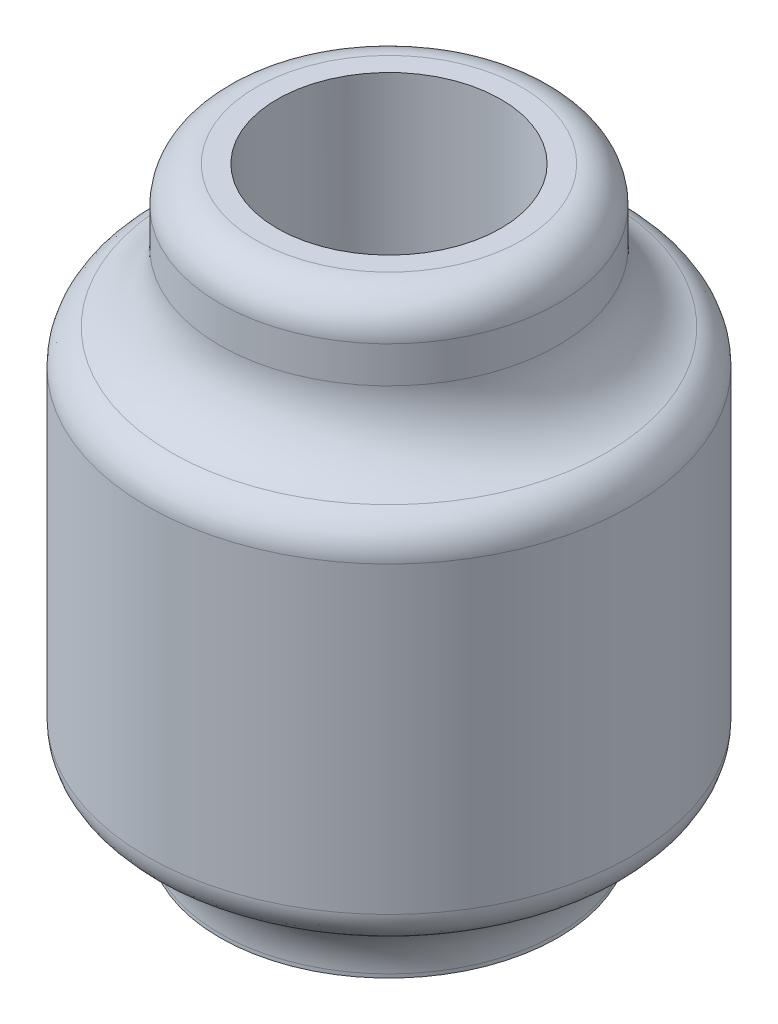
SolidWorks part; units mm, degrees
ref_plane "Front Plane" through (0, 0, 0) normal (0, 0, 1) x (1, 0, 0)
ref_plane "Top Plane" through (0, 0, 0) normal (0, 1, 0) x (1, 0, 0)
ref_plane "Right Plane" through (0, 0, 0) normal (1, 0, 0) x (0, 0, -1)
sketch "Sketch1" plane through (0, 0, 0) normal (0, 1, 0) x (1, 0, 0)
  circle A0 centre (0, 0) radius 6.15
  circle A1 centre (0, 0) radius 9.3
  dimension "D1" = 12.3
  dimension "D2" = 18.6
extrude "Boss-Extrude1" add sketch "Sketch1" along normal blind 12.2
sketch "Sketch2" plane through (0, 12.2, 0) normal (0, 1, 0) x (1, 0, 0)
  circle A0 centre (0, 0) radius 6.15 construction
  circle A1 centre (0, 0) radius 9.3
  circle A2 centre (0, 0) radius 9.3
  circle A3 centre (0, 0) radius 6.15
  dimension "D1" = 0
extrude "Boss-Extrude2" add sketch "Sketch2" along normal blind 12 from offset 4 separate body
sketch "Sketch3" plane through (0, 12.2, 0) normal (0, 1, 0) x (1, 0, 0)
  circle A2 centre (0, 0) radius 13.3
  circle A3 centre (0, 0) radius 13.3
  circle A4 centre (0, 0) radius 12.3
  dimension "D2" = 1
  dimension "D1" = 4
extrude "Boss-Extrude3" add sketch "Sketch3" along normal blind 10 and the other way blind 6 separate body
sketch "Sketch4" plane through (0, 22.2, 0) normal (0, 1, 0) x (1, 0, 0)
  circle A0 centre (0, 0) radius 9.3
  circle A1 centre (0, 0) radius 13.3
  circle A2 centre (0, 0) radius 13.3
  circle A3 centre (0, 0) radius 9.3 construction
  dimension "D2" = 0
  dimension "D1" = 0
extrude "Boss-Extrude4" add sketch "Sketch4" along normal blind 2
sketch "Sketch5" plane through (0, 0, 0) normal (0, -1, 0) x (1, 0, 0)
  line L1 (0.8029, 2.2849) -> (11.4839, 2.2849)
  line L2 (0.8029, 2.2849) -> (0.8029, -1.7151)
  line L3 (0.8029, -1.7151) -> (11.4839, -1.7151)
  line L4 (11.4839, 2.2849) -> (11.4839, -1.7151)
  line L5 (0.8029, 2.2849) -> (11.4839, -1.7151) construction
  line L6 (0.8029, -1.7151) -> (11.4839, 2.2849) construction
  line L7 (-2, 0.3278) -> (2, 0.3278)
  line L8 (-2, 0.3278) -> (-2, -12.6278)
  line L9 (-2, -12.6278) -> (2, -12.6278)
  line L10 (2, 0.3278) -> (2, -12.6278)
  line L11 (-2, 0.3278) -> (2, -12.6278) construction
  line L12 (-2, -12.6278) -> (2, 0.3278) construction
  line L13 (-2.4261, 2) -> (-9.8739, 2)
  line L14 (-2.4261, 2) -> (-2.4261, -2)
  line L15 (-2.4261, -2) -> (-9.8739, -2)
  line L16 (-9.8739, 2) -> (-9.8739, -2)
  line L17 (-2.4261, 2) -> (-9.8739, -2) construction
  line L18 (-2.4261, -2) -> (-9.8739, 2) construction
  line L19 (-2, 1.9767) -> (2, 1.9767)
  line L20 (-2, 1.9767) -> (-2, 10.3233)
  line L21 (-2, 10.3233) -> (2, 10.3233)
  line L22 (2, 1.9767) -> (2, 10.3233)
  line L23 (-2, 1.9767) -> (2, 10.3233) construction
  line L24 (-2, 10.3233) -> (2, 1.9767) construction
  circle A0 centre (0, 0) radius 6.15 construction
  point P0 (6.1434, 0.2849)
  point P7 (0, -6.15)
  point P12 (-6.15, 0)
  point P17 (0, 6.15)
  circle M5 centre (0, 0) radius 9.3
  circle M6 centre (0, 0) radius 6.15
  dimension "D1" = 4
  dimension "D2" = 4
  dimension "D3" = 4
  dimension "D4" = 4
extrude "Cut-Extrude1" cut sketch "Sketch5" against normal blind 6 from offset 6 contours L3 L1 M6 M5 | L10 L8 M6 M5 | L15 L13 M6 M5 | L22 L20 M6 M5 region at (7.6269, 0, 0.2919) region at (0, 0, 7.6329) region at (-7.6329, 0, 0) region at (0, 0, -7.6329) offset against normal yes
sketch "Sketch6" plane through (0, 0, 0) normal (0, -1, 0) x (1, 0, 0)
  line L1 (-2, -0.1222) -> (2, -0.1222)
  line L2 (-2, -0.1222) -> (-2, -12.1778)
  line L3 (-2, -12.1778) -> (2, -12.1778)
  line L4 (2, -0.1222) -> (2, -12.1778)
  line L5 (-2, -0.1222) -> (2, -12.1778) construction
  line L6 (-2, -12.1778) -> (2, -0.1222) construction
  line L7 (1.8378, 2) -> (10.4622, 2)
  line L8 (1.8378, 2) -> (1.8378, -2)
  line L9 (1.8378, -2) -> (10.4622, -2)
  line L10 (10.4622, 2) -> (10.4622, -2)
  line L11 (1.8378, 2) -> (10.4622, -2) construction
  line L12 (1.8378, -2) -> (10.4622, 2) construction
  line L13 (-1.6491, 2) -> (-10.6509, 2)
  line L14 (-1.6491, 2) -> (-1.6491, -2)
  line L15 (-1.6491, -2) -> (-10.6509, -2)
  line L16 (-10.6509, 2) -> (-10.6509, -2)
  line L17 (-1.6491, 2) -> (-10.6509, -2) construction
  line L18 (-1.6491, -2) -> (-10.6509, 2) construction
  line L19 (2, 14.7464) -> (-2, 14.7464)
  line L20 (2, 14.7464) -> (2, 3.8536)
  line L21 (2, 3.8536) -> (-2, 3.8536)
  line L22 (-2, 14.7464) -> (-2, 3.8536)
  line L23 (2, 14.7464) -> (-2, 3.8536) construction
  line L24 (2, 3.8536) -> (-2, 14.7464) construction
  circle A0 centre (0, 0) radius 6.15 construction
  circle A1 centre (0, 0) radius 9.3 construction
  point P0 (0, -6.15)
  point P7 (6.15, 0)
  point P12 (-6.15, 0)
  point P17 (0, 9.3)
  circle M5 centre (0, 0) radius 9.3
  circle M6 centre (0, 0) radius 6.15
  dimension "D1" = 4
  dimension "D2" = 4
  dimension "D3" = 4
  dimension "D4" = 4
extrude "Cut-Extrude2" cut sketch "Sketch6" against normal blind 6 from offset 16 contours L4 L2 M6 M5 | L15 L13 M6 M5 | L22 L20 M5 M6 | L9 L7 M6 M5 region at (0, 0, -7.6329) region at (-7.6329, 0, 0) region at (7.6329, 0, 0) region at (0, 0, 7.6329) offset against normal yes
sketch "Sketch7" plane through (0, 16.2, 0) normal (0, -1, 0) x (1, 0, 0)
  circle A0 centre (0, 0) radius 9.3
extrude "Boss-Extrude5" add sketch "Sketch7" along normal blind 4
sketch "Sketch8" plane through (0, 6.2, 0) normal (0, -1, 0) x (1, 0, 0)
  circle A0 centre (0, 0) radius 13.3
  circle A1 centre (0, 0) radius 9.3
  circle A2 centre (0, 0) radius 9.3 construction
  dimension "D1" = 0
extrude "Boss-Extrude6" add sketch "Sketch8" along normal blind 2
sketch "Sketch9" plane through (0, 28.2, 0) normal (0, 1, 0) x (1, 0, 0)
  circle A0 centre (0, 0) radius 6.15 construction
  circle A1 centre (0, 0) radius 9.3
  circle A2 centre (0, 0) radius 9.3
  circle A3 centre (0, 0) radius 6.15
  dimension "D1" = 0
extrude "Boss-Extrude7" add sketch "Sketch9" along normal blind 4
fillet "Fillet1" radius 4 1 edges at (0, 4.2, -9.3)
fillet "Fillet2" radius 4 1 edges at (0, 24.2, 9.3)
fillet "Fillet3" radius 2 1 edges at (0, 32.2, 9.3)
fillet "Fillet4" radius 2 1 edges at (0, 24.2, 13.3)
fillet "Fillet5" radius 2 1 edges at (0, 4.2, -13.3)
